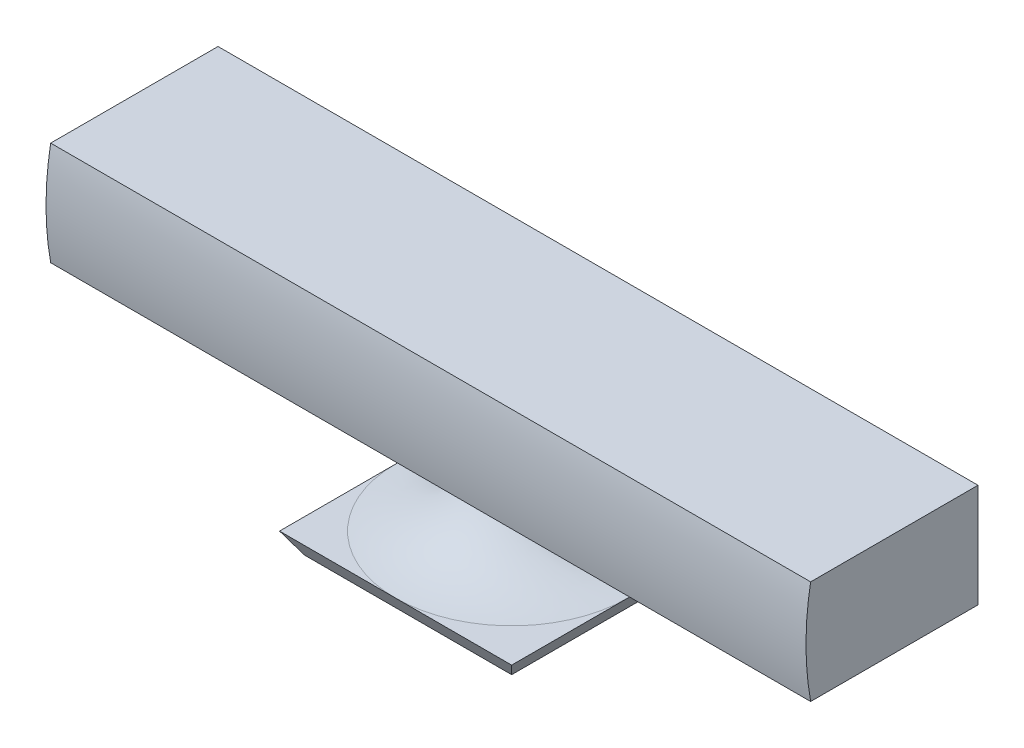
SolidWorks part; units mm, degrees
ref_plane "Front Plane" through (0, 0, 0) normal (0, 0, 1) x (1, 0, 0)
ref_plane "Top Plane" through (0, 0, 0) normal (0, 1, 0) x (1, 0, 0)
ref_plane "Right Plane" through (0, 0, 0) normal (1, 0, 0) x (0, 0, -1)
sketch "Sketch1" plane through (0, 0, 0) normal (0, 0, 1) x (1, 0, 0)
  line L1 (-139.7, -19.05) -> (139.7, -19.05)
  line L2 (-139.7, -19.05) -> (-139.7, 19.05)
  line L3 (-139.7, 19.05) -> (139.7, 19.05)
  line L4 (139.7, -19.05) -> (139.7, 19.05)
  line L5 (-139.7, -19.05) -> (139.7, 19.05) construction
  line L6 (-139.7, 19.05) -> (139.7, -19.05) construction
  point P0 (0, 0)
  dimension "D1" = 279.4
  dimension "D2" = 38.1
extrude "Boss-Extrude1" add sketch "Sketch1" along normal blind 31.75 and the other way blind 31.75
sketch "Sketch2" plane through (0, -19.05, 0) normal (0, -1, 0) x (1, 0, 0)
  line L1 (-42.672, -42.672) -> (42.672, -42.672)
  line L2 (-42.672, -42.672) -> (-42.672, 42.672)
  line L3 (-42.672, 42.672) -> (42.672, 42.672)
  line L4 (42.672, -42.672) -> (42.672, 42.672)
  line L5 (-42.672, -42.672) -> (42.672, 42.672) construction
  line L6 (-42.672, 42.672) -> (42.672, -42.672) construction
  point P0 (0, 0)
  dimension "D1" = 85.344
  dimension "D2" = 85.344
extrude "Boss-Extrude2" add sketch "Sketch2" along normal blind 38.1
sketch "Sketch3" plane through (0, 0, 0) normal (0, 0, 1) x (1, 0, 0)
  line L0 (0, -19.05) -> (0, -57.15) construction
  line L3 (-42.672, -57.15) -> (-42.672, -19.05) construction
  line L4 (42.672, -19.05) -> (-42.672, -19.05) construction
  line L6 (-42.672, -49.5177) -> (-67.103, -49.5177)
  line L7 (-67.103, -49.5177) -> (-67.103, -19.05)
  line L8 (-139.7, -19.05) -> (-42.672, -19.05) construction
  line L9 (-67.103, -19.05) -> (-6.1676, -19.05)
  spline S0 degree 2 poles (-42.672, -49.5177) (-14.4066, -46.1231) (-6.1676, -19.05) knots 0 0 0 1 1 1
revolve "Cut-Revolve8" cut sketch "Sketch3" angle 360 about L0
sketch "Sketch5" plane through (0, 0, 42.672) normal (0, 0, 1) x (1, 0, 0)
  line L0 (0, -49.5177) -> (0, -59.2713) construction
  line L1 (0, -57.15) -> (-38.1, -57.15) construction
  line L2 (42.672, -57.15) -> (-42.672, -57.15) construction
  line L3 (0, -57.15) -> (38.1, -57.15) construction
  line L4 (-38.1, -57.15) -> (-42.672, -49.5177)
  line L5 (-42.672, -49.5177) -> (-42.672, -57.15)
  line L6 (-42.672, -57.15) -> (-38.1, -57.15)
  line L7 (38.1, -57.15) -> (42.672, -49.5177)
  line L8 (42.672, -49.5177) -> (42.672, -57.15)
  line L9 (42.672, -57.15) -> (38.1, -57.15)
  dimension "D1" = 38.1
  dimension "D2" = 38.1
extrude "Cut-Extrude3" cut sketch "Sketch5" against normal through all
sketch "Sketch6" plane through (0, 0, 0) normal (1, 0, 0) x (0, 0, -1)
  line L0 (0, -49.5177) -> (0, -57.15) construction
  line L1 (42.672, -57.15) -> (-42.672, -57.15) construction
  line L2 (-42.672, -49.5177) -> (-42.672, -57.15)
  line L3 (0, -57.15) -> (-38.1, -57.15) construction
  line L4 (-38.1, -57.15) -> (-42.672, -49.5177)
  line L5 (-42.672, -57.15) -> (-38.1, -57.15)
  line L6 (42.672, -49.5177) -> (42.672, -57.15)
  line L7 (42.672, -57.15) -> (38.1, -57.15)
  line L8 (38.1, -57.15) -> (42.672, -49.5177)
  dimension "D1" = 38.1
extrude "Cut-Extrude4" cut sketch "Sketch6" against normal through all and the other way through all
sketch "Sketch7" plane through (139.7, 0, 0) normal (1, 0, 0) x (0, 0, -1)
  line L0 (31.75, 19.05) -> (-31.75, 19.05) construction
  line L2 (31.75, -19.05) -> (-31.75, -19.05) construction
  line L3 (-29.7784, 19.05) -> (-31.75, 19.05)
  line L4 (-31.75, 19.05) -> (-31.75, -19.05)
  line L5 (-31.75, -19.05) -> (-29.7784, -19.05)
  spline S0 degree 2 poles (-29.7784, 19.05) (-33.2223, -0.0037) (-29.7784, -19.05) knots 0 0 0 1 1 1
extrude "Cut-Extrude5" cut sketch "Sketch7" against normal through all
